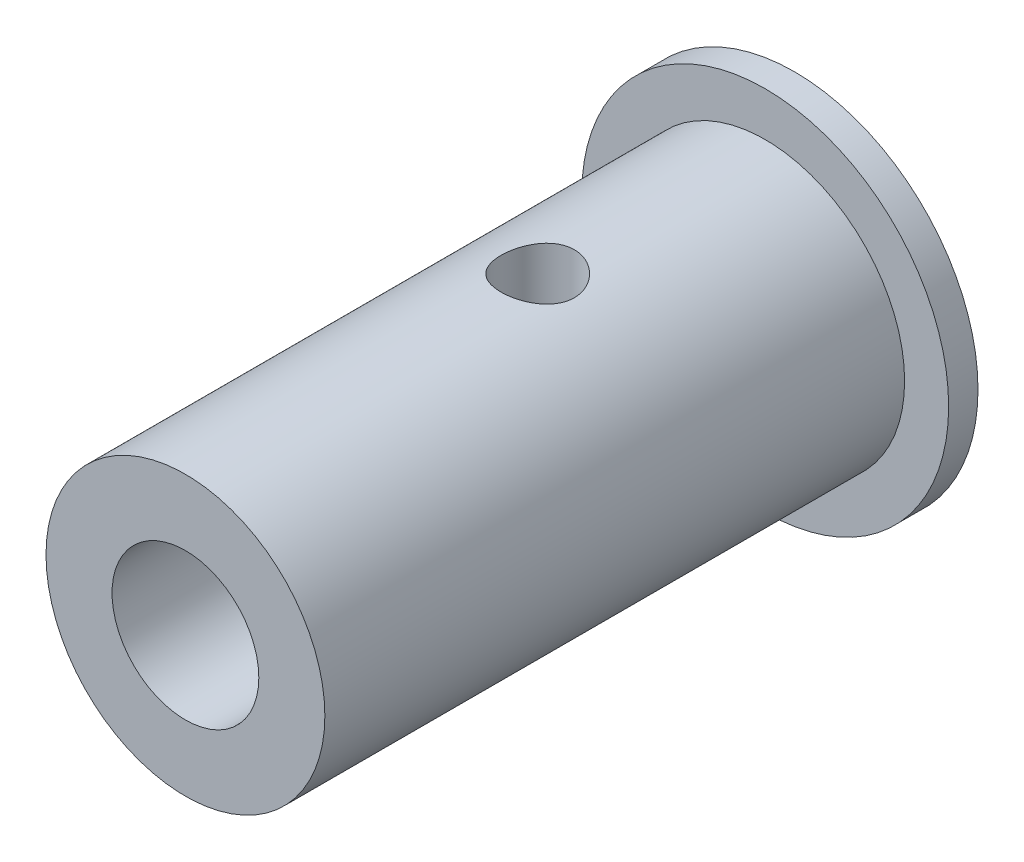
SolidWorks part; units mm, degrees
material "Aluminum Bronze"
ref_plane "Front Plane" through (0, 0, 0) normal (0, 0, 1) x (1, 0, 0)
ref_plane "Top Plane" through (0, 0, 0) normal (0, 1, 0) x (1, 0, 0)
ref_plane "Right Plane" through (0, 0, 0) normal (1, 0, 0) x (0, 0, -1)
sketch "Sketch1" plane through (0, 0, 0) normal (0, 0, 1) x (1, 0, 0)
  circle A0 centre (0, 0) radius 12.5
  circle A1 centre (0, 0) radius 9.5
  circle A2 centre (0, 0) radius 5
  dimension "D1" = 25
  dimension "D2" = 19
  dimension "D3" = 10
extrude "Boss-Extrude1" add sketch "Sketch1" along normal blind 2 contours A0 A1 region at (-12.1464, 0, 0)
extrude "Boss-Extrude2" add sketch "Sketch1<3>" along normal blind 41.5 contours A1 A2 region at (-9.2313, 0, 0)
sketch "Sketch1<3>" plane through (0, 0, 0) normal (0, 0, 1) x (1, 0, 0) same geometry as "Sketch1"
sketch "Sketch2" plane through (0, 0, 0) normal (0, 1, 0) x (1, 0, 0)
  line L0 (0, 0) -> (0, -50000) construction
  circle A0 centre (0, -17.5) radius 2.5
  dimension "D1" = 5
  dimension "D2" = 17.5
extrude "Cut-Extrude1" cut sketch "Sketch2" along normal up to next
cosmetic thread "Cosmetic Thread1" parameters "D2"=6
